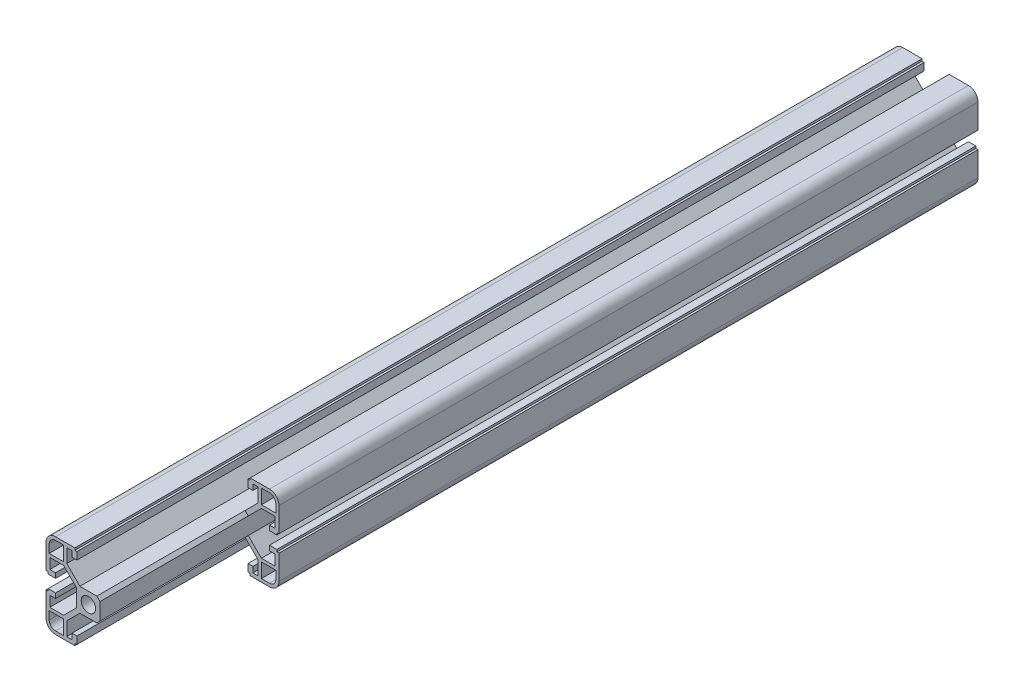
SolidWorks part; units mm, degrees
material "6061-T6 (SS)"
ref_plane "Front Plane" through (0, 0, 0) normal (0, 0, 1) x (1, 0, 0)
ref_plane "Top Plane" through (0, 0, 0) normal (0, 1, 0) x (1, 0, 0)
ref_plane "Right Plane" through (0, 0, 0) normal (1, 0, 0) x (0, 0, -1)
sketch "Sketch1" plane through (0, 0, 0) normal (0, 0, 1) x (1, 0, 0)
  line L0 (3.4, 0) -> (5.5, 0)
  line L1 (10.19, 11.69) -> (4, 5.5)
  line L2 (11.69, 10.19) -> (5.5, 4)
  line L3 (18.2, 10.19) -> (11.69, 10.19)
  line L4 (18.2, 10.19) -> (18.2, 5.2656)
  line L5 (18.2, 5.2656) -> (15.5, 5.2656)
  line L6 (15.5, 5.2656) -> (15.5, 2.9656)
  line L7 (15.5, 2.9656) -> (19, 2.9656)
  line L8 (19, 2.9656) -> (19, 3.9656)
  line L9 (19, 3.9656) -> (20, 3.9656)
  line L10 (20, 3.9656) -> (20, 15.5)
  line L11 (15.5, 20) -> (6.3853, 20)
  line L12 (18.5, 11.69) -> (18.5, 15.5)
  line L13 (15.5, 18.5) -> (11.69, 18.5)
  line L14 (11.69, 11.69) -> (11.69, 18.5)
  line L15 (0, 3.4) -> (0, 5.5)
  line L16 (4, 5.5) -> (0, 5.5)
  line L17 (6.3853, 20) -> (6.3853, 19)
  line L18 (5.5, 0) -> (5.5, 4)
  line L19 (6.3853, 19) -> (5.3853, 19)
  line L20 (5.3853, 19) -> (5.3853, 15.5)
  line L21 (5.3853, 15.5) -> (7.6853, 15.5)
  line L22 (10.19, 11.69) -> (10.19, 18.2)
  line L23 (11.69, 11.69) -> (18.5, 11.69)
  line L24 (7.6853, 18.2) -> (7.6853, 15.5)
  line L25 (10.19, 18.2) -> (7.6853, 18.2)
  arc A0 (20, 15.5) -> (15.5, 20) centre (15.5, 15.5) ccw
  arc A1 (18.5, 15.5) -> (15.5, 18.5) centre (15.5, 15.5) ccw
  arc A2 (3.4, 0) -> (0, 3.4) centre (0, 0) ccw
  dimension "D3" = 4.5
  dimension "D18" = 1.5
  dimension "D9" = 3.4
  dimension "D20" = 1.8
  dimension "D25" = 3
  dimension "D1" = 5.5
  dimension "D2" = 1.5
  dimension "D4" = 14.5
  dimension "D5" = 1.5
  dimension "D6" = 2.1
  dimension "D7" = 2.3
  dimension "D8" = 1.8
  dimension "D10" = 6.81
  dimension "D11" = 2.1
  dimension "D12" = 1
  dimension "D13" = 4.5
  dimension "D14" = 45
  dimension "D15" = 14.5
  dimension "D16" = 1
  dimension "D17" = 1.5
  dimension "D19" = 6.81
  dimension "D21" = 4.5
  dimension "D22" = 2.3
  dimension "D23" = 1
  dimension "D24" = 1
  dimension "D26" = 8.754
  dimension "D27" = 8.754
  dimension "D28" = 4.9244
  dimension "D29" = 2.5047
extrude "Boss-Extrude1" add sketch "Sketch1" along normal blind 400
mirror "Mirror1" about plane through (0, 0, 0) normal (0, 1, 0) of "Boss-Extrude1"
mirror "Mirror2" about plane through (0, 0, 0) normal (1, 0, 0) of "Boss-Extrude1"
mirror "Mirror3" about plane through (0, 0, 0) normal (0, 1, 0) of "Mirror2"
sketch "Croquis2" plane through (0, 0, 400) normal (0, 0, 1) x (1, 0, 0)
  line L0 (4, 5.5) -> (5.5, 4)
  line L1 (5.5, 4) -> (5.5, -4)
  line L2 (5.5, -4) -> (4, -5.5)
  line L3 (4, -5.5) -> (4, -23.2335)
  line L4 (4, -23.2335) -> (29.7306, -23.2335)
  line L5 (29.7306, -23.2335) -> (29.7306, 32.1268)
  line L6 (29.7306, 32.1268) -> (4, 32.1268)
  line L7 (4, 32.1268) -> (4, 5.5)
extrude "Cortar-Extruir2" cut sketch "Croquis2" against normal blind 70
